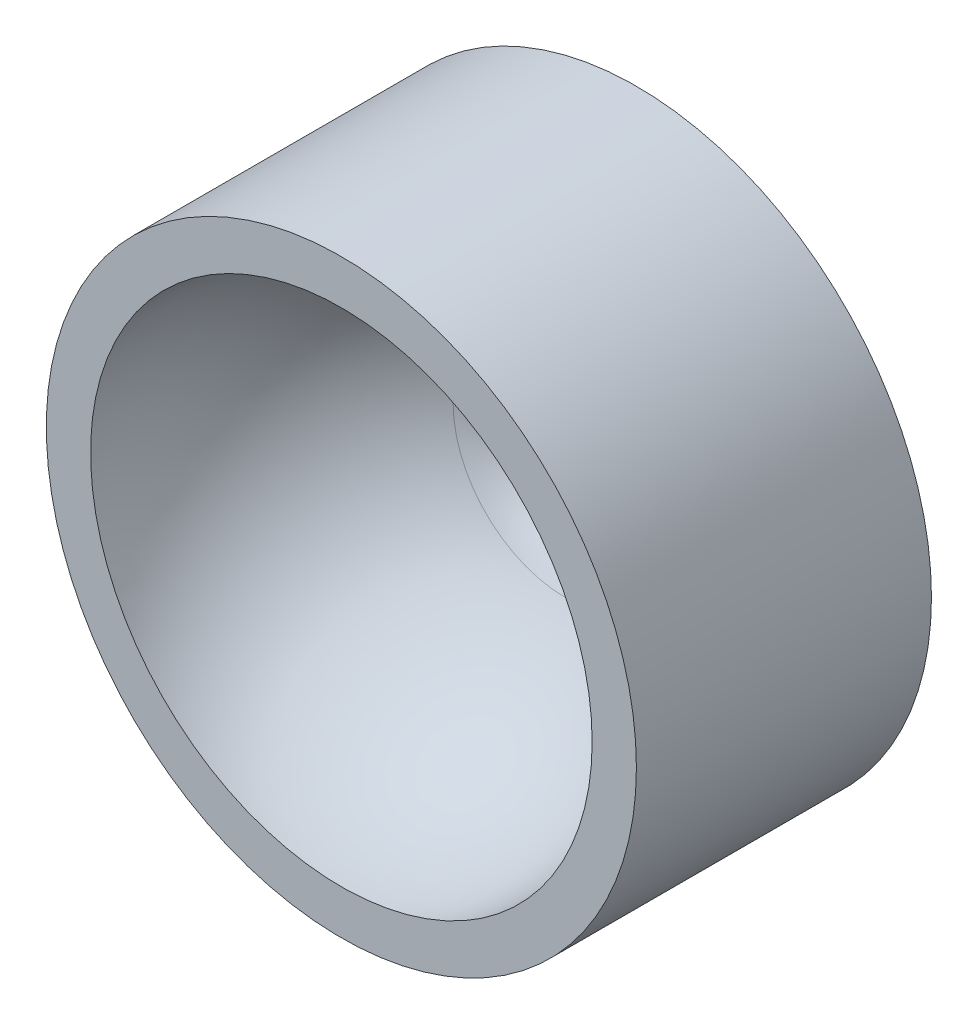
SolidWorks part; units mm, degrees
ref_plane "Front Plane" through (0, 0, 0) normal (0, 0, 1) x (1, 0, 0)
ref_plane "Top Plane" through (0, 0, 0) normal (0, 1, 0) x (1, 0, 0)
ref_plane "Right Plane" through (0, 0, 0) normal (1, 0, 0) x (0, 0, -1)
sketch "Sketch1" plane through (0, 0, 0) normal (0, 0, 1) x (1, 0, 0)
  circle A0 centre (0, 0) radius 10
  dimension "D1" = 20
extrude "Boss-Extrude1" add sketch "Sketch1" along normal blind 10
sketch "Sketch2" plane through (0, 0, 10) normal (0, 0, 1) x (1, 0, 0)
  line L0 (0, 8.5) -> (0, -8.5)
  arc A0 (0, 8.5) -> (0, -8.5) centre (0, 0) cw
  circle A1 centre (0, 0) radius 10 construction
  dimension "D2" = 8.5
  dimension "D1" = 17
  dimension "D3" = 8.5
revolve "Cut-Revolve1" cut sketch "Sketch2" angle 360 about L0
sketch "Sketch3" plane through (0, 0, 0) normal (0, 0, -1) x (-1, 0, 0)
  circle A0 centre (0, 0) radius 1.5
  dimension "D1" = 3
extrude "Cut-Extrude1" cut sketch "Sketch3" against normal blind 8
fillet "Fillet1" radius 5 1 edges at (1.5, 0, 1.6334)
